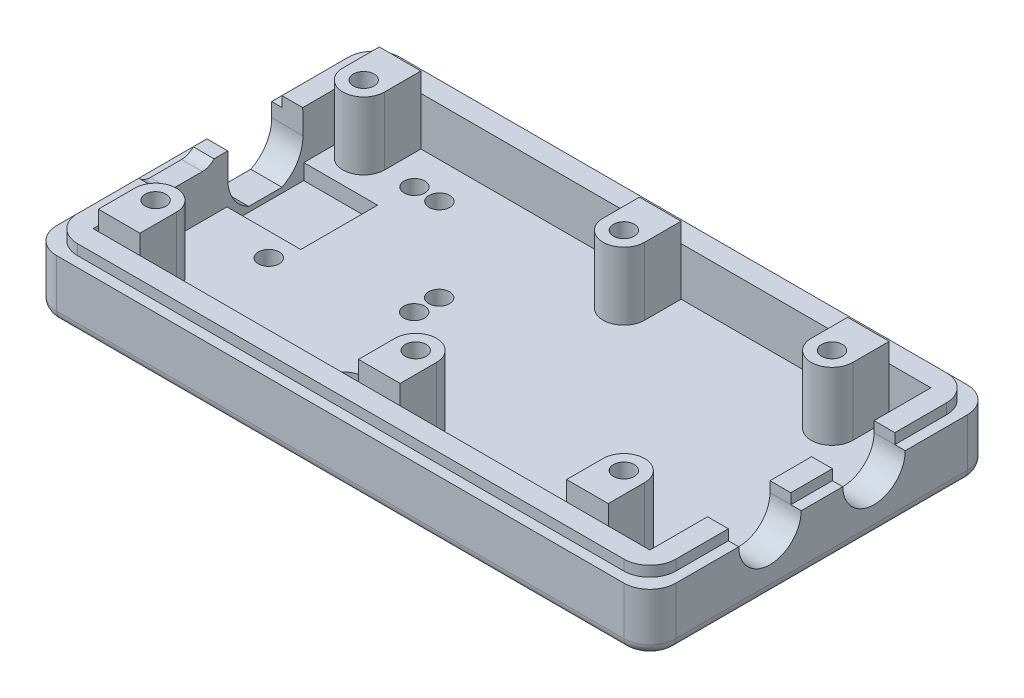
SolidWorks part; units mm, degrees
note: The reader was unsure of these and kept them because the rebuilt part matched: shared geometry of "Sketch1<2>".
ref_plane "Front Plane" through (0, 0, 0) normal (0, 0, 1) x (1, 0, 0)
ref_plane "Top Plane" through (0, 0, 0) normal (0, 1, 0) x (1, 0, 0)
ref_plane "Right Plane" through (0, 0, 0) normal (1, 0, 0) x (0, 0, -1)
sketch "Sketch1" plane through (0, 0, 0) normal (0, 1, 0) x (1, 0, 0)
  line L1 (-54.5, -33) -> (54.5, -33)
  line L2 (-59.5, -28) -> (-59.5, 28)
  line L3 (-54.5, 33) -> (54.5, 33)
  line L4 (59.5, -28) -> (59.5, 28)
  line L5 (-59.5, -33) -> (59.5, 33) construction
  line L6 (-59.5, 33) -> (59.5, -33) construction
  line L7 (-53.5, -27) -> (53.5, -27)
  line L8 (-53.5, -27) -> (-53.5, 27)
  line L9 (-53.5, 27) -> (53.5, 27)
  line L10 (53.5, -27) -> (53.5, 27)
  line L11 (-53.5, -27) -> (53.5, 27) construction
  line L12 (-53.5, 27) -> (53.5, -27) construction
  arc A0 (54.5, 33) -> (59.5, 28) centre (54.5, 28) cw
  arc A1 (54.5, -33) -> (59.5, -28) centre (54.5, -28) ccw
  arc A2 (-54.5, -33) -> (-59.5, -28) centre (-54.5, -28) cw
  arc A3 (-59.5, 28) -> (-54.5, 33) centre (-54.5, 28) cw
  point P0 (0, 0)
  point P6 (0, 0)
  dimension "D5" = 5
  dimension "D1" = 119
  dimension "D2" = 66
  dimension "D3" = 6
  dimension "D4" = 6
extrude "Boss-Extrude1" add sketch "Sketch1" along normal blind 9.25
extrude "Boss-Extrude2" add sketch "Sketch1<2>" against normal blind 4 contours A2 L2 A3 L3 A0 L4 A1 L1
sketch "Sketch1<2>" plane through (0, 0, 0) normal (0, 1, 0) x (1, 0, 0) same geometry as "Sketch1"
fillet "Fillet1" radius 2 8 edges at (58.0355, -4, 31.5355) (59.5, -4, 0) (58.0355, -4, -31.5355) (0, -4, -33) (-58.0355, -4, -31.5355) (-59.5, -4, 0) (-58.0355, -4, 31.5355) (0, -4, 33)
sketch "Sketch2" plane through (0, 0, 0) normal (0, 1, 0) x (1, 0, 0)
  line L0 (-52.5, 27) -> (-52.5, 20)
  line L1 (53.5, 27) -> (-53.5, 27) construction
  line L2 (-44.5, 20) -> (-44.5, 27)
  line L3 (-52.5, 27) -> (-44.5, 27)
  line L4 (-2.5, 27) -> (-2.5, 20)
  line L5 (5.5, 20) -> (5.5, 27)
  line L6 (37.5, 27) -> (37.5, 20)
  line L7 (45.5, 20) -> (45.5, 27)
  line L8 (45.5, 27) -> (37.5, 27)
  line L9 (5.5, 27) -> (-2.5, 27)
  line L10 (-53.5, 27) -> (-53.5, -27) construction
  line L11 (-9.3411, 0) -> (9.3411, 0) construction
  line L12 (5.5, -27) -> (-2.5, -27)
  line L13 (45.5, -27) -> (37.5, -27)
  line L14 (45.5, -20) -> (45.5, -27)
  line L15 (37.5, -27) -> (37.5, -20)
  line L16 (5.5, -20) -> (5.5, -27)
  line L17 (-2.5, -27) -> (-2.5, -20)
  line L18 (-52.5, -27) -> (-44.5, -27)
  line L19 (-44.5, -20) -> (-44.5, -27)
  line L20 (-52.5, -27) -> (-52.5, -20)
  arc A0 (-52.5, 20) -> (-44.5, 20) centre (-48.5, 20) ccw
  arc A1 (-2.5, 20) -> (5.5, 20) centre (1.5, 20) ccw
  arc A2 (37.5, 20) -> (45.5, 20) centre (41.5, 20) ccw
  arc A4 (37.5, -20) -> (45.5, -20) centre (41.5, -20) cw
  arc A5 (-2.5, -20) -> (5.5, -20) centre (1.5, -20) cw
  arc A6 (-52.5, -20) -> (-44.5, -20) centre (-48.5, -20) cw
  circle A9 centre (-48.5, 20) radius 2
  circle A10 centre (1.5, 20) radius 2
  circle A11 centre (41.5, 20) radius 2
  circle A12 centre (-48.5, -20) radius 2
  circle A13 centre (1.5, -20) radius 2
  circle A14 centre (41.5, -20) radius 2
  dimension "D1" = 5
  dimension "D6" = 4
  dimension "D2" = 8
  dimension "D3" = 7
  dimension "D4" = 50
  dimension "D5" = 40
extrude "Boss-Extrude3" add sketch "Sketch2" along normal up to vertex (16 mm away)
sketch "Sketch3" plane through (0, 0, 0) normal (0, 1, 0) x (1, 0, 0)
  circle A0 centre (-18, 4) radius 2
  circle A1 centre (-18, -0.8) radius 2
  circle A2 centre (-41, -5.75) radius 2
  circle A3 centre (-34, 20.05) radius 2
  circle A4 centre (-38.8, 20.05) radius 2
  circle A5 centre (-12.5, -9.5) radius 3
  circle A6 centre (-12.5, -19.5) radius 3
  point P21 (0, 0)
  point P22 (0, 0)
  point P23 (0, 0)
  point P24 (0, 0)
  point P25 (0, 0)
  point P26 (0, 0)
  point P27 (0, 0)
  point P28 (-38.8, 20.05)
  point P30 (-34, 20.05)
  point P32 (-18, 4)
  point P34 (-18, -0.8)
  point P36 (-41, -5.75)
  point P38 (-12.5, -9.5)
  point P40 (-12.5, -19.5)
  dimension "D1" = 6
  dimension "D2" = 6
  dimension "D3" = 4
  dimension "D4" = 4
  dimension "D5" = 4
  dimension "D6" = 4
  dimension "D7" = 4
extrude "Cut-Extrude1" cut sketch "Sketch3" against normal blind 14
sketch "Sketch4" plane through (59.5, 0, 0) normal (1, 0, 0) x (0, 0, -1)
  line L0 (-28, 9.25) -> (28, 9.25) construction
  line L2 (-15.92, 7.2688) -> (-15.92, 9.25)
  line L3 (-15.92, 9.25) -> (-3.92, 9.25)
  line L4 (-3.92, 7.2688) -> (-3.92, 9.25)
  line L7 (4.08, 7.2688) -> (4.08, 9.25)
  line L8 (4.08, 9.25) -> (16.08, 9.25)
  line L9 (16.08, 7.2688) -> (16.08, 9.25)
  arc A0 (-15.92, 7.2688) -> (-3.92, 7.2688) centre (-9.92, 7.2688) ccw
  arc A1 (4.08, 7.2688) -> (16.08, 7.2688) centre (10.08, 7.2688) ccw
  point P1 (16.08, 14.5)
  point P2 (0, 0)
  point P4 (0, 0)
  point P16 (0, 0)
  point P17 (0, 0)
  point P18 (0, 0)
  point P19 (0, 0)
  point P20 (-9.92, 7.2688)
  point P22 (10.08, 7.2688)
  dimension "D1" = 12
  dimension "D2" = 12
extrude "Cut-Extrude2" cut sketch "Sketch4" against normal blind 6 contours L3 A0 | L8 A1
sketch "Sketch6" plane through (-59.5, 0, 0) normal (-1, 0, 0) x (0, 0, 1)
  line L3 (-28, 9.25) -> (28, 9.25) construction
  line L7 (-9.2851, -2.0176) -> (-2.9149, -2.0176)
  line L8 (-9.143, -1.0176) -> (-7.9274, -1.0176) construction
  line L9 (-13.3259, 4.5368) -> (-13.2322, 14.5)
  line L10 (-13.2322, 14.5) -> (1.1262, 9.25)
  line L11 (1.1262, 9.25) -> (1.1262, 4.4688)
  arc A2 (-2.9149, -2.0176) -> (1.1262, 4.4688) centre (-6.1, 4.4688) ccw
  arc A3 (-3.057, -1.0176) -> (-9.143, -1.0176) centre (-6.1, 4.4688) ccw construction
  arc A4 (-13.3259, 4.5368) -> (-9.2851, -2.0176) centre (-6.1, 4.4688) ccw
  point P20 (-13.2322, 3.8688)
  point P27 (-13.3709, 4.4688)
  point P28 (-13.3738, 4.6741)
  point P29 (-13.3259, 14.5)
  dimension "D5" = 0.9524
  dimension "D6" = 1
extrude "Cut-Extrude3" cut sketch "Sketch6" against normal blind 6
sketch "Sketch7" plane through (0, 0, 0) normal (0, 1, 0) x (1, 0, 0)
  line L1 (-39.32, 13.4787) -> (-53.5, 13.4787)
  line L2 (-39.32, 13.4787) -> (-39.32, -1.2787)
  line L3 (-39.32, -1.2787) -> (-53.5, -1.2787)
  line L4 (-53.5, 13.4787) -> (-53.5, -1.2787)
  line L7 (-53.671, -1.2787) -> (-51.152, -1.2787) construction
  line L8 (-53.5, 20) -> (-53.5, -20) construction
  line L9 (-53.671, 13.4787) -> (-51.152, 13.4787) construction
  point P5 (0, 0)
  point P6 (-39.32, 0.3609)
  point P7 (-39.32, -1.2787)
  point P8 (-53.5, -1.2787)
  point P9 (-52.5428, 13.3004)
  point P10 (-53.671, 13.4787)
  point P11 (0, 0)
  point P15 (0, 0)
  point P17 (-53.5, 13.4787)
extrude "Cut-Extrude4" cut sketch "Sketch7" against normal blind 3
sketch "Sketch8" plane through (0, 9.25, 0) normal (0, 1, 0) x (1, 0, 0)
  line L0 (54.5, 33) -> (-54.5, 33) construction
  line L1 (-52.5, -31) -> (52.5, -31)
  line L2 (-57.5, -26) -> (-57.5, 26)
  line L3 (-52.5, 31) -> (52.5, 31)
  line L4 (57.5, -26) -> (57.5, 26)
  line L5 (-57.5, -31) -> (57.5, 31) construction
  line L6 (-57.5, 31) -> (57.5, -31) construction
  line L7 (-59.5, 28) -> (-59.5, 13.2816) construction
  arc A0 (52.5, 31) -> (57.5, 26) centre (52.5, 26) cw
  arc A1 (52.5, -31) -> (57.5, -26) centre (52.5, -26) ccw
  arc A2 (-52.5, -31) -> (-57.5, -26) centre (-52.5, -26) cw
  arc A3 (-57.5, 26) -> (-52.5, 31) centre (-52.5, 26) cw
  point P0 (0, 0)
  dimension "D3" = 5
  dimension "D1" = 2
  dimension "D2" = 2
extrude "Cut-Extrude5" cut sketch "Sketch8" against normal blind 2 flip side to cut
sketch "Sketch9" plane through (0, 7.25, 0) normal (0, 1, 0) x (1, 0, 0)
  line L0 (-57.5, -1.1262) -> (-57.5, -26) construction
  line L1 (-57.5, -3.2) -> (-59.5, -3.2)
  line L2 (-57.5, -3.2) -> (-57.5, -14.8)
  line L3 (-57.5, -14.8) -> (-59.5, -14.8)
  line L4 (-59.5, -3.2) -> (-59.5, -14.8)
  line L5 (-59.5, -1.1262) -> (-59.5, -28) construction
  line L6 (-57.7, -3) -> (-59.5, -3) construction
  line L7 (-57.7, -15) -> (-59.5, -15) construction
  dimension "D1" = 0.2
  dimension "D2" = 0.2
extrude "Boss-Extrude4" [suppressed] add sketch "Sketch9" along normal blind 2
sketch "Sketch10" plane through (-57.5, 0, 0) normal (-1, 0, 0) x (0, 0, 1)
  line L1 (3, 13.3313) -> (15, 13.3313)
  line L2 (3, 13.3313) -> (3, 11.25)
  line L3 (6, 8.25) -> (12, 8.25)
  line L4 (15, 13.3313) -> (15, 11.25)
  line L5 (15, 11.25) -> (15, 7.25) construction
  line L6 (6, 14.25) -> (12, 14.25) construction
  line L7 (3, 9.45) -> (3, 7.25) construction
  arc A0 (12, 8.25) -> (15, 11.25) centre (12, 11.25) ccw
  arc A1 (3, 11.25) -> (6, 8.25) centre (6, 11.25) ccw
  point P4 (2.4064, 11.2789)
  point P5 (0, 0)
  point P10 (0, 0)
  point P11 (0, 0)
  point P14 (3, 13.3313)
  point P17 (15, 8.25)
  point P20 (3, 8.25)
  dimension "D2" = 3
  dimension "D1" = 6
extrude "Cut-Extrude6" cut sketch "Sketch10" against normal up to next
sketch "Sketch11" plane through (0, -4, 0) normal (0, -1, 0) x (1, 0, 0)
  line L0 (-51.2003, -20.05) -> (-40.8, -20.05) construction
  line L1 (-7.5, 31) -> (-7.5, -1.1664) construction
  line L2 (54.5, 31) -> (-54.5, 31) construction
  line L3 (-23, 31) -> (-23, -25.9753) construction
  line L4 (-46, 31) -> (-46, -31) construction
  line L5 (-54.5, -31) -> (54.5, -31) construction
  line L6 (-29, -31) -> (-29, -3.6567) construction
  line L7 (-45.8, -3.6567) -> (-45.8, -31) construction
  circle A0 centre (-38.8, -20.05) radius 2 construction
  circle A1 centre (-12.5, 19.5) radius 3 construction
  circle A2 centre (-18, 0.8) radius 2 construction
  circle A3 centre (-41, 5.75) radius 2 construction
  circle A5 centre (-34, -20.05) radius 2 construction
  text T0 " Over-range   " font "Century Gothic" height in points 8
  text T1 "    x10/x100  BW Limit" font "Century Gothic" height in points 8
  text T2 "                               x10      x100" font "Century Gothic" height in points 8
  text T3 "                          Power" font "Century Gothic" height in points 8
  text T4 "              BW Limit" font "Century Gothic" height in points 8
  dimension "D1" = 5
  dimension "D2" = 5
  dimension "D3" = 5
  dimension "D5" = 5
  dimension "D4" = 5
extrude "Cut-Extrude7" cut sketch "Sketch11" against normal blind 1.5
